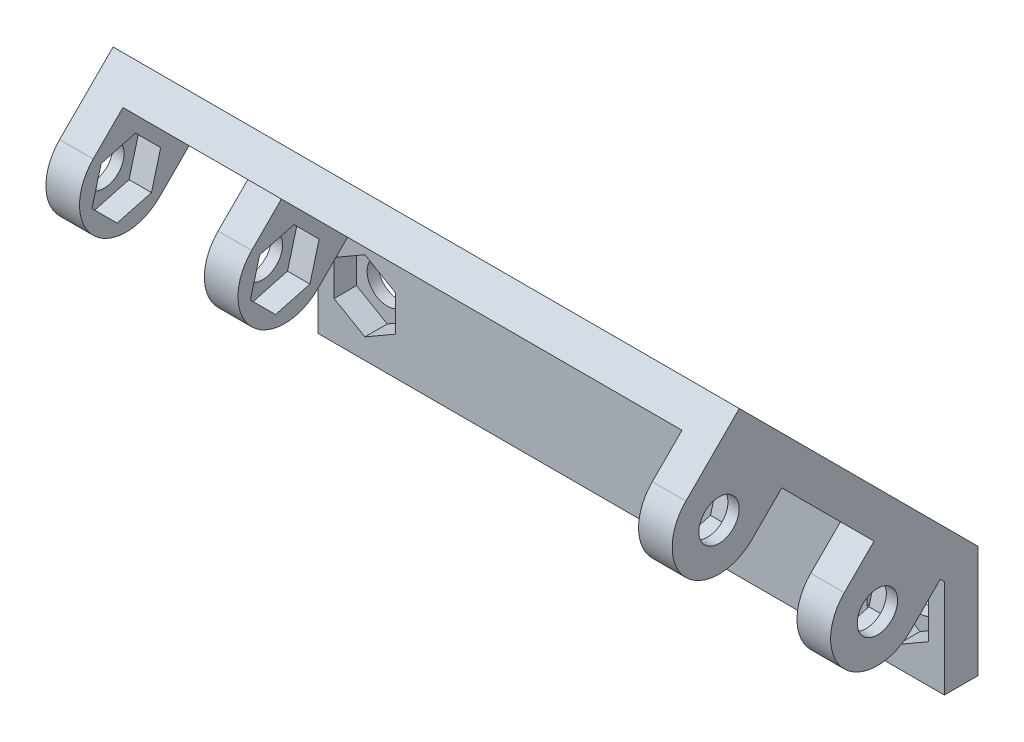
SolidWorks part; units mm, degrees
ref_plane "Front Plane" through (0, 0, 0) normal (0, 0, 1) x (1, 0, 0)
ref_plane "Top Plane" through (0, 0, 0) normal (0, 1, 0) x (1, 0, 0)
ref_plane "Right Plane" through (0, 0, 0) normal (1, 0, 0) x (0, 0, -1)
sketch "Sketch1" plane through (0, 0, 0) normal (0, 0, 1) x (1, 0, 0)
  line L1 (70.0719, -10) -> (14.1792, -10)
  line L2 (70.0719, -10) -> (70.0719, 0)
  line L3 (70.0719, 0) -> (14.1792, 0)
  line L4 (14.1792, -10) -> (14.1792, 0)
extrude "Boss-Extrude1" add sketch "Sketch1" along normal blind 3
sketch "Sketch2" plane through (0, 0, 3) normal (0, 0, 1) x (1, 0, 0)
  line L2 (22.5208, -10) -> (22.5208, 0) construction
  line L3 (14.1792, 0) -> (14.1792, -10) construction
  line L6 (22.5208, -10) -> (22.5208, 0) construction
  line L7 (14.1792, 0) -> (14.1792, -10) construction
  line L8 (42.1255, 0) -> (42.1255, -10) construction
  line L15 (70.0719, 0) -> (14.1792, 0) construction
  line L25 (14.1792, -10) -> (70.0719, -10) construction
  line L26 (14.1792, -5) -> (22.5208, -5) construction
  line L27 (65.9011, -8.1754) -> (63.1511, -6.5877)
  line L28 (21.1, -6.5877) -> (21.1, -3.4123)
  line L29 (21.1, -3.4123) -> (18.35, -1.8246)
  line L30 (18.35, -1.8246) -> (15.6, -3.4123)
  line L31 (15.6, -3.4123) -> (15.6, -6.5877)
  line L32 (15.6, -6.5877) -> (18.35, -8.1754)
  line L33 (18.35, -8.1754) -> (21.1, -6.5877)
  line L34 (68.6511, -6.5877) -> (65.9011, -8.1754)
  line L35 (68.6511, -3.4123) -> (68.6511, -6.5877)
  line L36 (65.9011, -1.8246) -> (68.6511, -3.4123)
  line L37 (63.1511, -3.4123) -> (65.9011, -1.8246)
  line L38 (63.1511, -6.5877) -> (63.1511, -3.4123)
  circle A0 centre (18.35, -5) radius 2.75 construction
  circle A1 centre (65.9011, -5) radius 2.75 construction
  point P14 (15.6, -5)
  dimension "D1" = 5.5
extrude "Cut-Extrude1" cut sketch "Sketch2" against normal blind 2
sketch "Sketch3" plane through (0, 0, 3) normal (0, 0, 1) x (1, 0, 0)
  point P8 (18.35, -5)
  point P11 (65.9011, -5)
hole_wizard "M3 Clearance Hole1" positions "Sketch3" profile "Sketch4" hole size "M3" standard "ANSI Metric" end condition through all
sketch "Sketch4" plane through (18.35, -5, 3) normal (1, 0, 0) x (0, -1, 0)
  line L0 (0, 0) -> (0, 3)
  line L1 (0, 3) -> (1.8, 3)
  line L2 (1.8, 3) -> (1.8, 0)
  line L5 (1.8, 0) -> (0, 0)
  line L11 (0, -6.35) -> (0, 107.95) construction
  dimension "Thru Hole Dia." = 3.6
  dimension "Thru Hole Depth" = 3
sketch "Sketch5" plane through (14.1792, 0, 0) normal (-1, 0, 0) x (0, 0, 1)
  line L0 (0, 0) -> (21.299, 21.299)
  line L1 (21.299, 21.299) -> (23.4203, 19.1777)
  line L2 (23.4203, 19.1777) -> (3, -1.2426)
  line L3 (3, 0) -> (3, -10) construction
  line L4 (3, 0) -> (0, 0) construction
  line L5 (3, 0) -> (22.799, 19.799) construction
  line L6 (3, -1.2426) -> (3, 0)
  line L7 (3, 0) -> (0, 0)
  dimension "D1" = 45
  dimension "D2" = 3
  dimension "D3" = 28
extrude "Boss-Extrude2" add sketch "Sketch5" against normal up to surface (55.8926 mm away) up to face at (70.0719, -5, 1.5)
sketch "Sketch6" plane through (14.1792, 0, 0) normal (-1, 0, 0) x (0, 0, 1)
  line L0 (23.4203, 19.1777) -> (17.5154, 13.2727)
  line L1 (3, -1.2426) -> (23.4203, 19.1777) construction
  line L2 (23.4203, 19.1777) -> (26.072, 16.526)
  line L3 (17.5154, 13.2727) -> (20.167, 10.6211)
  line L4 (11.2754, 11.2754) -> (13.3968, 9.1541) construction
  line L5 (20.8741, 11.3282) -> (23.9413, 10.5063)
  line L6 (23.9413, 10.5063) -> (26.1867, 12.7517)
  line L7 (26.1867, 12.7517) -> (25.3649, 15.8189)
  line L8 (25.3649, 15.8189) -> (22.2976, 16.6408)
  line L9 (22.2976, 16.6408) -> (20.0523, 14.3954)
  line L10 (20.0523, 14.3954) -> (20.8741, 11.3282)
  line L12 (21.299, 21.299) -> (0, 0) construction
  line L13 (5.9101, 0.2533) -> (8.1555, 2.4986)
  line L14 (6.732, -2.814) -> (5.9101, 0.2533)
  line L15 (9.7992, -3.6358) -> (6.732, -2.814)
  line L16 (12.0446, -1.3904) -> (9.7992, -3.6358)
  line L17 (11.2227, 1.6768) -> (12.0446, -1.3904)
  line L18 (8.1555, 2.4986) -> (11.2227, 1.6768)
  line L19 (3.3732, -0.8694) -> (6.0249, -3.5211)
  line L20 (3.3732, -0.8694) -> (9.2782, 5.0355)
  line L21 (9.2782, 5.0355) -> (11.9298, 2.3839)
  arc A0 (26.072, 16.526) -> (20.167, 10.6211) centre (23.1195, 13.5735) cw
  circle A2 centre (23.1195, 13.5735) radius 2.75 construction
  circle A3 centre (8.9774, -0.5686) radius 2.75 construction
  arc A4 (6.0249, -3.5211) -> (11.9298, 2.3839) centre (8.9774, -0.5686) ccw
  line M10 (3, -1.2426) -> (23.4203, 19.1777)
  dimension "D3" = 3.75
  dimension "D1" = 1
  dimension "D4" = 5.5
  dimension "D5" = 10
extrude "Boss-Extrude3" add sketch "Sketch6" against normal blind 3 contours L19 A4 L21 L13 L18 L17 L16 L15 L14 M10 | L18 L13 L14 L15 L16 L17 | L9 L10 L5 L6 L7 L8 | A0 L2 L3 L10 L9 L8 L7 L6 L5 M10 region at (14.1792, 17.754, 24.6483) region at (14.1792, 3.6119, 10.5062) region at (14.1792, 13.5735, 23.1195) region at (14.1792, -0.5686, 8.9774)
ref_plane "Plane1" through (42.1255, 0, 0) normal (-1, 0, 0) x (0, 0, 1)
mirror "Mirror1" about plane through (42.1255, 0, 0) normal (-1, 0, 0) of "Boss-Extrude3"
sketch "Sketch7" plane through (14.1792, 0, 0) normal (-1, 0, 0) x (0, 0, 1)
  point P0 (8.9774, -0.5686)
  point P3 (23.1195, 13.5735)
hole_wizard "M3 Clearance Hole2" positions "Sketch7" profile "Sketch8" hole size "M3" standard "ANSI Metric" end condition through all
sketch "Sketch8" plane through (14.1792, -0.5686, 8.9774) normal (0, 1, 0) x (0, 0, 1)
  line L0 (0, 0) -> (0, 55.8926)
  line L1 (0, 55.8926) -> (1.8, 55.8926)
  line L2 (1.8, 55.8926) -> (1.8, 0)
  line L5 (1.8, 0) -> (0, 0)
  line L11 (0, -6.35) -> (0, 107.95) construction
  dimension "Thru Hole Dia." = 3.6
  dimension "Thru Hole Depth" = 55.8926
extrude "Cut-Extrude2" cut sketch "Sketch6<3>" along normal blind 2 from surface contours L18 L13 L14 L15 L16 L17 | L9 L10 L5 L6 L7 L8 region at (14.1792, 13.5735, 23.1195) region at (14.1792, -0.5686, 8.9774) starting at face at (17.1792, -2.3686, 8.9774)
sketch "Sketch6<3>" plane through (14.1792, 0, 0) normal (-1, 0, 0) x (0, 0, 1) same geometry as "Sketch6"
extrude "Cut-Extrude3" cut sketch "Sketch6<4>" against normal blind 2 from surface contours L9 L10 L5 L6 L7 L8 | L18 L13 L14 L15 L16 L17 region at (14.1792, 13.5735, 23.1195) region at (14.1792, -0.5686, 8.9774) starting at face at (67.0719, 15.3735, 23.1195)
sketch "Sketch6<4>" plane through (14.1792, 0, 0) normal (-1, 0, 0) x (0, 0, 1) same geometry as "Sketch6"
